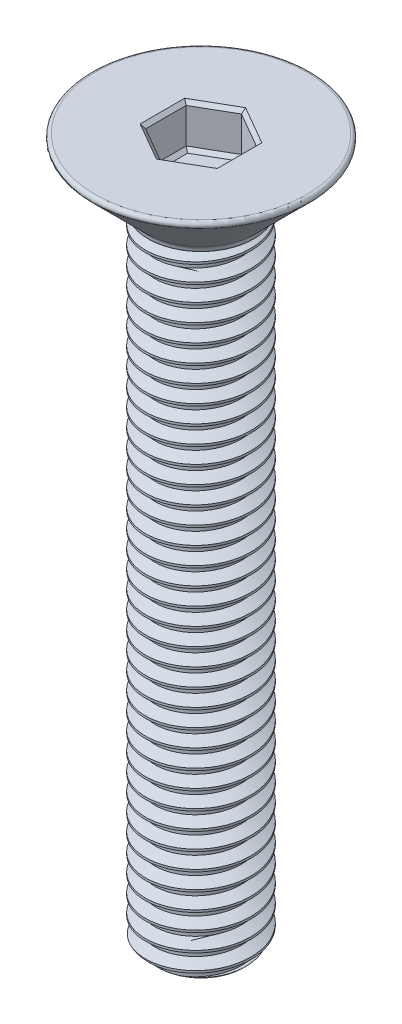
SolidWorks part; units mm, degrees
material "AISI Type A2 Tool Steel"
ref_plane "Front Plane" through (0, 0, 0) normal (0, 0, 1) x (1, 0, 0)
ref_plane "Top Plane" through (0, 0, 0) normal (0, 1, 0) x (1, 0, 0)
ref_plane "Right Plane" through (0, 0, 0) normal (1, 0, 0) x (0, 0, -1)
sketch "Sketch1" plane through (0, 0, 0) normal (0, 1, 0) x (1, 0, 0)
  circle A0 centre (0, 0) radius 1.5
  dimension "D1" = 3
extrude "Boss-Extrude1" add sketch "Sketch1" along normal blind 18.14
thread "Thread1" pitch 0.5 method cut profile "Thread Profile1" start angle 0, offset 1, length 0, pitch 0.5, diameter 3
ref_plane "Plane1" through (-1.5, 19.14, 0) normal (0, 0, 1) x (-1, 0, 0)
sketch "Thread Profile1" plane through (-1.5, 19.14, 0) normal (0, 0, 1) x (-1, 0, 0)
  line L0 (0, 0) -> (0, 0.5) construction
  line L11 (0, 0) -> (0, 0.4375)
  line L12 (0, 0.4375) -> (-0.2706, 0.2812)
  line L13 (-0.2706, 0.2812) -> (-0.2706, 0.1562)
  line L15 (-0.2706, 0.1562) -> (0, 0)
  line L17 (-0.2706, 0.2187) -> (0, 0.2187) construction
  point P2 (0, 0)
  dimension "Pitch" = 0.5
  dimension "Profile_Angle" = 60
  dimension "Profile_Land" = 0.125
  dimension "Profile_Height" = 0.2706
sketch "Sketch5" plane through (0, 18.14, 0) normal (0, 1, 0) x (1, 0, 0)
  circle A0 centre (0, 0) radius 1.5
  dimension "D1" = 3
extrude "Boss-Extrude2" add sketch "Sketch5" along normal blind 0.1
sketch "Sketch6" plane through (0, 18.24, 0) normal (0, 1, 0) x (1, 0, 0)
  circle A0 centre (0, 0) radius 1.5
  dimension "D1" = 3
extrude "Boss-Extrude3" add sketch "Sketch6" along normal blind 1.76 draft 45 draft outward yes
sketch "Sketch7" plane through (0, 0, 0) normal (0, 0, 1) x (1, 0, 0)
  line L0 (0, 0) -> (0, 0.1997) construction
  line L1 (0, 0) -> (1.51, 0) construction
  line L2 (1.51, 0) -> (1.51, 0.3)
  line L3 (1.51, 0.3) -> (1.21, 0)
  line L4 (1.21, 0) -> (1.51, 0)
  dimension "D1" = 45
  dimension "D2" = 0.3
  dimension "D3" = 1.51
revolve "Cut-Revolve1" cut sketch "Sketch7" angle 360 about L0
fillet "Fillet1" radius 0.1 1 edges at (0, 20, 3.26)
fillet "Fillet2" radius 0.2 1 edges at (0, 18.24, 1.5)
sketch "Sketch8" plane through (0, 20, 0) normal (0, 1, 0) x (1, 0, 0)
  line L1 (0, 1.1547) -> (-1, 0.5774)
  line L2 (-1, 0.5774) -> (-1, -0.5774)
  line L3 (-1, -0.5774) -> (0, -1.1547)
  line L4 (0, -1.1547) -> (1, -0.5774)
  line L5 (1, -0.5774) -> (1, 0.5774)
  line L6 (1, 0.5774) -> (0, 1.1547)
  circle A0 centre (0, 0) radius 1 construction
  dimension "D1" = 2
extrude "Cut-Extrude1" cut sketch "Sketch8" against normal blind 1.1
chamfer "Chamfer1" distance 0.1 angle 45 6 edges at (-1, 20, 0) (-0.5, 20, 0.866) (0.5, 20, 0.866) (1, 20, 0) (0.5, 20, -0.866) (-0.5, 20, -0.866)
sketch "Sketch9" plane through (0, 18.9, 0) normal (0, 1, 0) x (1, 0, 0)
  line L1 (0, 1.1547) -> (-1, 0.5774)
  line L2 (-1, 0.5774) -> (-1, -0.5774)
  line L3 (-1, -0.5774) -> (0, -1.1547)
  line L4 (0, -1.1547) -> (1, -0.5774)
  line L5 (1, -0.5774) -> (1, 0.5774)
  line L6 (1, 0.5774) -> (0, 1.1547)
  circle A0 centre (0, 0) radius 1 construction
extrude "Cut-Extrude2" cut sketch "Sketch9" against normal blind 0.1 draft 45
